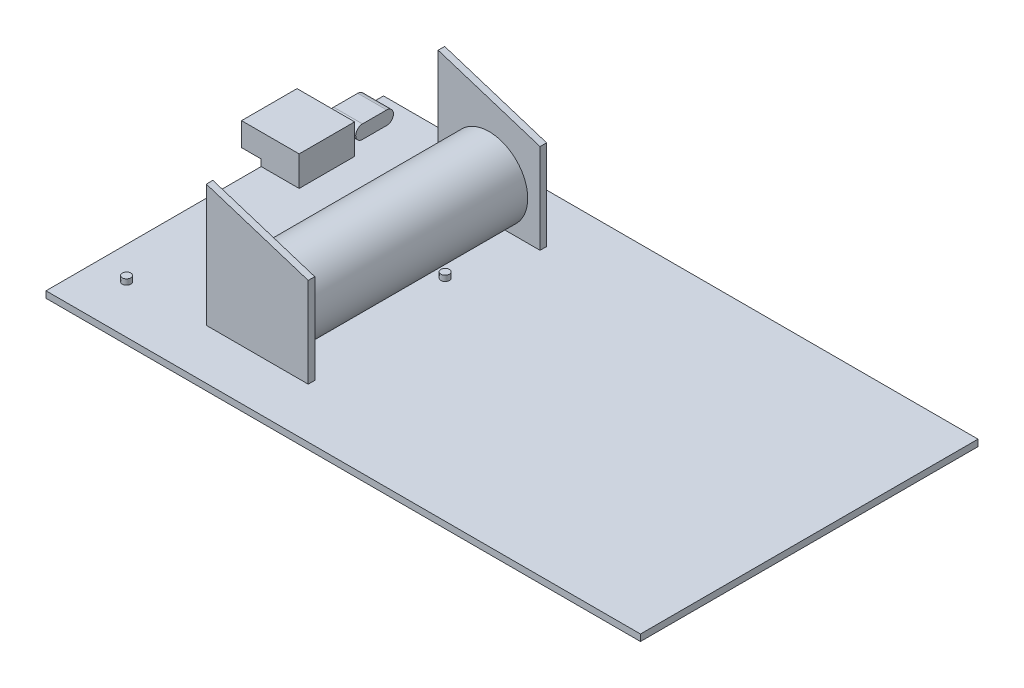
SolidWorks part; units mm, degrees
ref_plane "Front Plane" through (0, 0, 0) normal (0, 0, 1) x (1, 0, 0)
ref_plane "Top Plane" through (0, 0, 0) normal (0, 1, 0) x (1, 0, 0)
ref_plane "Right Plane" through (0, 0, 0) normal (1, 0, 0) x (0, 0, -1)
sketch "Sketch1" plane through (0, 0, 0) normal (0, 1, 0) x (1, 0, 0)
  line L1 (-70.45, -40) -> (70.45, -40)
  line L2 (-70.45, -40) -> (-70.45, 40)
  line L3 (-70.45, 40) -> (70.45, 40)
  line L4 (70.45, -40) -> (70.45, 40)
  line L5 (-70.45, -40) -> (70.45, 40) construction
  line L6 (-70.45, 40) -> (70.45, -40) construction
  point P0 (0, 0)
  dimension "D1" = 140.9
  dimension "D2" = 80
extrude "PCB" add sketch "Sketch1" along normal blind 1.55
sketch "Sketch2" plane through (-70.45, 0, 0) normal (-1, 0, 0) x (0, 0, 1)
  line L0 (-31.43, 1.55) -> (-31.43, 3.15)
  line L1 (-40, 1.55) -> (40, 1.55) construction
  line L2 (-40, 1.55) -> (-40, 0) construction
  dimension "D1" = 1.6
  dimension "D2" = 8.57
sketch "Sketch3" plane through (-70.45, 0, 0) normal (-1, 0, 0) x (0, 0, 1)
  line L0 (-34.3, 3.15) -> (-28.56, 3.15) construction
  line L1 (-34.3, 4.75) -> (-28.56, 4.75)
  line L2 (-34.3, 1.55) -> (-28.56, 1.55)
  arc A0 (-34.3, 4.75) -> (-34.3, 1.55) centre (-34.3, 3.15) ccw
  arc A1 (-28.56, 1.55) -> (-28.56, 4.75) centre (-28.56, 3.15) ccw
  point P2 (-31.43, 3.15)
  dimension "D1" = 5.74
extrude "bodyC" add sketch "Sketch3" against normal blind 6.45 and the other way blind 0.4
sketch "Sketch4" plane through (0, 1.55, 0) normal (0, 1, 0) x (1, 0, 0)
  line L0 (70.45, 40) -> (-70.45, 40) construction
  line L1 (-61.45, 11) -> (-75.1, 11)
  line L2 (-61.45, 11) -> (-61.45, 24.15)
  line L3 (-61.45, 24.15) -> (-75.1, 24.15)
  line L4 (-75.1, 11) -> (-75.1, 24.15)
  line L6 (-70.45, 28.56) -> (-70.45, -40) construction
  dimension "D1" = 13.65
  dimension "D2" = 13.15
  dimension "D3" = 15.85
  dimension "D4" = 4.65
extrude "Boss-Extrude4" add sketch "Sketch4" along normal blind 7.1 and the other way blind 1.55
sketch "Sketch5" plane through (0, 0, -11) normal (0, 0, 1) x (1, 0, 0)
  line L0 (-75.1, 0) -> (-75.1, 8.65) construction
  line L1 (-70.45, 0) -> (-75.1, 0)
  line L2 (-70.45, 0) -> (-70.45, 3.1)
  line L3 (-70.45, 3.1) -> (-75.1, 3.1)
  line L4 (-75.1, 0) -> (-75.1, 3.1)
  dimension "D1" = 3.1
extrude "Cut-Extrude3" cut sketch "Sketch5" against normal blind 14.1
sketch "Sketch11" plane through (0, 1.55, 0) normal (0, 1, 0) x (1, 0, 0)
  line L1 (-44.35, 26.85) -> (-20.2, 26.85)
  line L2 (-44.35, 26.85) -> (-44.35, 28.4)
  line L3 (-44.35, 28.4) -> (-20.2, 28.4)
  line L4 (-20.2, 26.85) -> (-20.2, 28.4)
  line L6 (70.45, 40) -> (-70.45, 40) construction
  line L7 (-70.45, 40) -> (-70.45, 34.3) construction
  dimension "D1" = 11.6
  dimension "D2" = 26.1
  dimension "D3" = 1.55
  dimension "D4" = 24.15
extrude "Boss-Extrude8" add sketch "Sketch11" along normal blind 29
sketch "Sketch7" plane through (0, 1.55, 0) normal (0, 1, 0) x (1, 0, 0)
  line L0 (-70.45, 11) -> (-70.45, -40) construction
  line L1 (-44.35, -28.1) -> (-20.2, -28.1)
  line L2 (-44.35, -28.1) -> (-44.35, -26.55)
  line L3 (-44.35, -26.55) -> (-20.2, -26.55)
  line L4 (-20.2, -28.1) -> (-20.2, -26.55)
  line L5 (-70.45, -40) -> (70.45, -40) construction
  dimension "D1" = 26.1
  dimension "D2" = 11.9
  dimension "D3" = 1.55
  dimension "D4" = 24.15
extrude "Boss-Extrude5" add sketch "Sketch7" along normal blind 29
sketch "Sketch8" plane through (0, 0, 28.1) normal (0, 0, 1) x (1, 0, 0)
  line L0 (-44.35, 30.55) -> (-20.2, 22.85)
  line L1 (-20.2, 30.55) -> (-20.2, 1.55) construction
  line L5 (-20.2, 30.55) -> (-44.35, 30.55)
  line L6 (-20.2, 22.85) -> (-20.2, 30.55)
extrude "Cut-Extrude4" cut sketch "Sketch8" against normal blind 89
sketch "Sketch12" plane through (0, 0, -26.85) normal (0, 0, 1) x (1, 0, 0)
  line L0 (-32.275, 1.55) -> (-32.275, 10.75)
  line L1 (-44.35, 1.55) -> (-20.2, 1.55) construction
  circle A0 centre (-32.275, 10.75) radius 9.15
  dimension "D1" = 9.2
extrude "Battery" add sketch "Sketch12" along normal blind 54 contours A0 region at (-25.988, 4.463, -26.85)
sketch "Sketch13" plane through (0, 1.55, 0) normal (0, 1, 0) x (1, 0, 0)
  line L0 (-70.45, -28.6) -> (-62.75, -28.6)
  line L1 (-70.45, 11) -> (-70.45, -40) construction
  line L2 (-70.45, -40) -> (70.45, -40) construction
  circle A0 centre (-62.75, -28.6) radius 1
  dimension "D1" = 7.7
  dimension "D2" = 11.4
extrude "Button" add sketch "Sketch13" along normal blind 1.3 contours A0
sketch "Sketch14" plane through (0, 1.55, 0) normal (0, 1, 0) x (1, 0, 0)
  line L0 (-33.45, 9.9) -> (-25.75, 9.9)
  line L3 (70.45, 40) -> (-70.45, 40) construction
  line L4 (70.45, -40) -> (70.45, 40) construction
  circle A0 centre (-25.75, 9.9) radius 1
  dimension "D3" = 96.2
  dimension "D2" = 30.1
  dimension "D1" = 7.7
extrude "Reset" add sketch "Sketch14" along normal blind 1.3 contours A0
